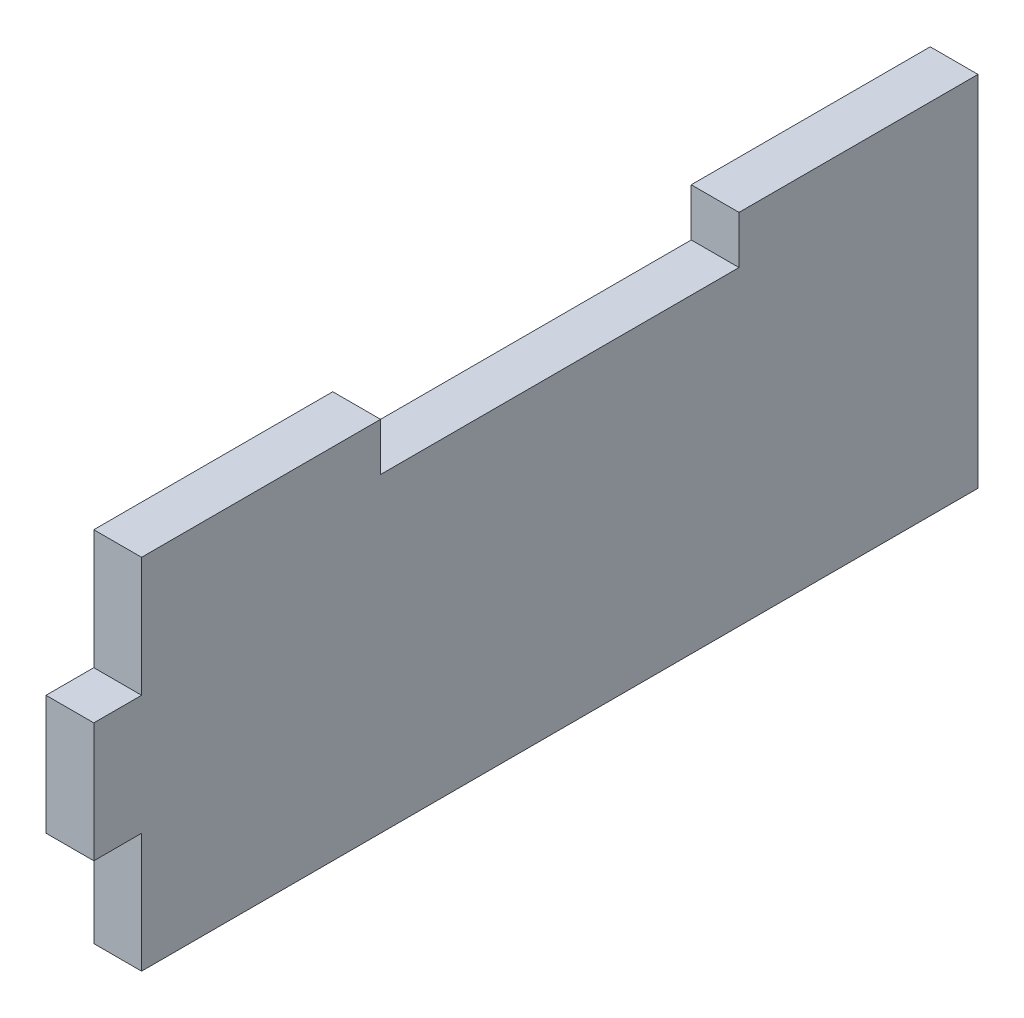
SolidWorks part; units mm, degrees
ref_plane "Front" through (0, 0, 0) normal (0, 0, 1) x (1, 0, 0)
ref_plane "Top" through (0, 0, 0) normal (0, 1, 0) x (1, 0, 0)
ref_plane "Right" through (0, 0, 0) normal (1, 0, 0) x (0, 0, -1)
sketch "Skizze1" plane through (0, 0, 0) normal (1, 0, 0) x (0, 0, -1)
  line L0 (0, 0) -> (74, 0) construction
  line L1 (0, -5) -> (0, 5)
  line L2 (0, 5) -> (4, 5)
  line L3 (4, 5) -> (4, 15)
  line L4 (4, 15) -> (74, 15)
  line L5 (74, 15) -> (74, -15)
  line L6 (4, -15) -> (74, -15)
  line L7 (4, -5) -> (4, -15)
  line L8 (0, -5) -> (4, -5)
  dimension "D1" = 4
  dimension "D2" = 10
  dimension "D3" = 30
  dimension "D4" = 70
extrude "Aufsatz-Linear austragen1" add sketch "Skizze1" along normal blind 4
sketch "Skizze2" [suppressed] plane through (4, 0, 0) normal (1, 0, 0) x (0, 0, -1)
  line L0 (39, 15) -> (39, 0) construction
  line L1 (4, 15) -> (24, 15)
  line L2 (4, 15) -> (4, 11)
  line L3 (4, 11) -> (24, 11)
  line L4 (24, 15) -> (24, 11)
  line L5 (74, 15) -> (54, 15)
  line L6 (74, 15) -> (74, 11)
  line L7 (74, 11) -> (54, 11)
  line L8 (54, 15) -> (54, 11)
  line L9 (74, 15) -> (4, 15) construction
  line L10 (39, 0) -> (0, 0) construction
  line L11 (54, -15) -> (54, -11)
  line L12 (74, -11) -> (54, -11)
  line L13 (74, -15) -> (74, -11)
  line L14 (74, -15) -> (54, -15)
  line L15 (24, -15) -> (24, -11)
  line L16 (4, -11) -> (24, -11)
  line L17 (4, -15) -> (4, -11)
  line L18 (4, -15) -> (24, -15)
  dimension "D1" = 4
  dimension "D2" = 30
extrude "Schnitt-Linear austragen1" [suppressed] cut sketch "Skizze2" against normal through all
sketch "Skizze3" plane through (4, 0, 0) normal (1, 0, 0) x (0, 0, -1)
  line L0 (74, 15) -> (4, 15) construction
  line L1 (24, 15) -> (54, 15)
  line L2 (24, 15) -> (24, 11)
  line L3 (24, 11) -> (54, 11)
  line L4 (54, 15) -> (54, 11)
  line L5 (39, -15) -> (39, 11) construction
  line L6 (4, -15) -> (74, -15) construction
  dimension "D1" = 4
  dimension "D2" = 30
extrude "Schnitt-Linear austragen2" cut sketch "Skizze3" against normal through all
